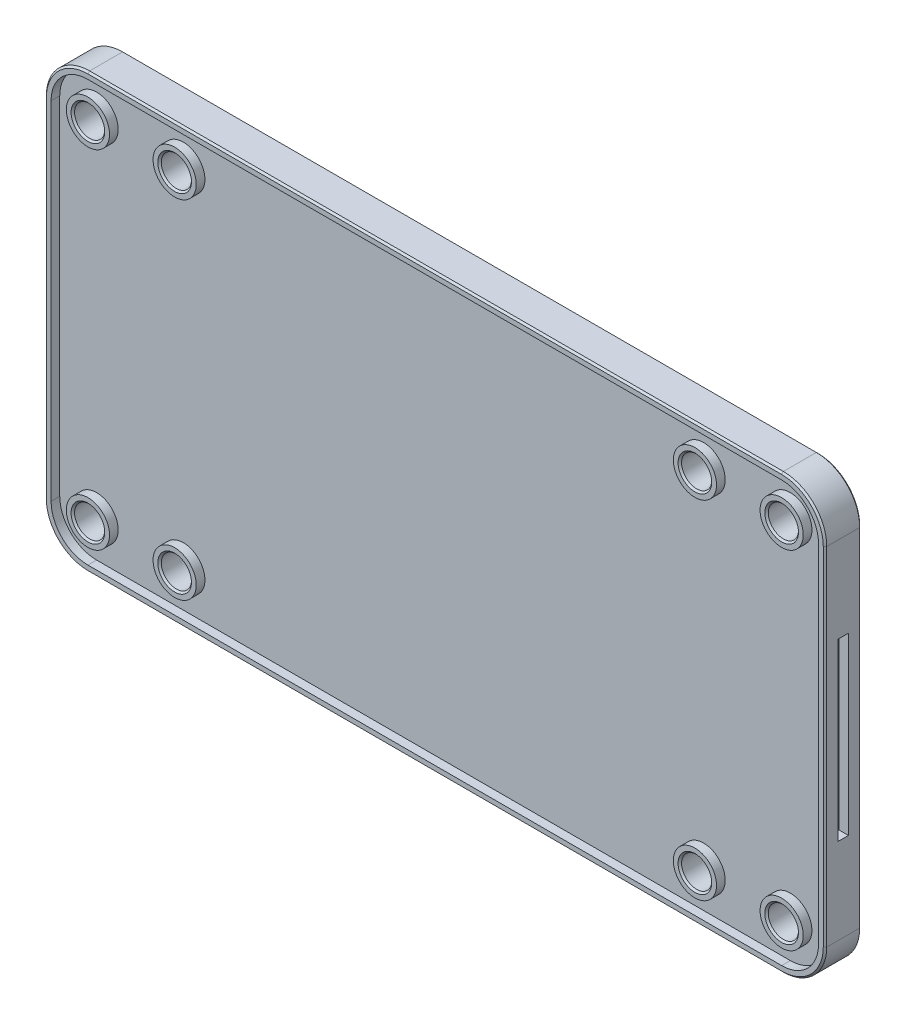
SolidWorks part; units mm, degrees
material "ABS"
ref_plane "Front Plane" through (0, 0, 0) normal (0, 0, 1) x (1, 0, 0)
ref_plane "Top Plane" through (0, 0, 0) normal (0, 1, 0) x (1, 0, 0)
ref_plane "Right Plane" through (0, 0, 0) normal (1, 0, 0) x (0, 0, -1)
sketch "Sketch1" plane through (0, 0, 0) normal (0, 0, 1) x (1, 0, 0)
  line L0 (-57.15, 0) -> (57.15, 0) construction
  line L1 (-50.8, -31.75) -> (50.8, -31.75)
  line L2 (-57.15, -25.4) -> (-57.15, 25.4)
  line L3 (-50.8, 31.75) -> (50.8, 31.75)
  line L4 (57.15, -25.4) -> (57.15, 25.4)
  line L5 (-57.15, -31.75) -> (57.15, 31.75) construction
  line L6 (-57.15, 31.75) -> (57.15, -31.75) construction
  line L7 (0, 31.75) -> (0, -31.75) construction
  arc A0 (50.8, 31.75) -> (57.15, 25.4) centre (50.8, 25.4) cw
  arc A1 (50.8, -31.75) -> (57.15, -25.4) centre (50.8, -25.4) ccw
  arc A2 (-50.8, -31.75) -> (-57.15, -25.4) centre (-50.8, -25.4) cw
  arc A3 (-57.15, 25.4) -> (-50.8, 31.75) centre (-50.8, 25.4) cw
  circle A4 centre (-50.8, -25.4) radius 2.2098
  circle A5 centre (-38.1, -25.4) radius 2.2098
  circle A6 centre (-50.8, 25.4) radius 2.2098
  circle A7 centre (-38.1, 25.4) radius 2.2098
  circle A8 centre (50.8, 25.4) radius 2.2098
  circle A9 centre (38.1, 25.4) radius 2.2098
  circle A10 centre (50.8, -25.4) radius 2.2098
  circle A11 centre (38.1, -25.4) radius 2.2098
  point P0 (0, 0)
  dimension "D3" = 6.35
  dimension "D4" = 4.4196
  dimension "D1" = 63.5
  dimension "D2" = 114.3
  dimension "D5" = 6.35
  dimension "D6" = 12.7
  dimension "D7" = 6.35
extrude "Boss-Extrude1" add sketch "Sketch1" against normal blind 3.175
sketch "Sketch2" plane through (0, 0, 0) normal (0, 0, 1) x (1, 0, 0)
  line L12 (50.8, 30.7975) -> (-50.8, 30.7975)
  line L13 (-56.1975, 25.4) -> (-56.1975, -25.4)
  line L14 (-50.8, -30.7975) -> (50.8, -30.7975)
  line L15 (56.1975, -25.4) -> (56.1975, 25.4)
  line L16 (50.8, 30.7975) -> (-50.8, 30.7975)
  line L17 (-56.1975, 25.4) -> (-56.1975, -25.4)
  line L18 (-50.8, -30.7975) -> (50.8, -30.7975)
  line L19 (56.1975, -25.4) -> (56.1975, 25.4)
  circle A0 centre (-50.8, -25.4) radius 2.2098 construction
  arc A8 (56.1975, 25.4) -> (50.8, 30.7975) centre (50.8, 25.4) ccw
  arc A9 (-50.8, 30.7975) -> (-56.1975, 25.4) centre (-50.8, 25.4) ccw
  arc A10 (-56.1975, -25.4) -> (-50.8, -30.7975) centre (-50.8, -25.4) ccw
  arc A11 (50.8, -30.7975) -> (56.1975, -25.4) centre (50.8, -25.4) ccw
  arc A12 (56.1975, 25.4) -> (50.8, 30.7975) centre (50.8, 25.4) ccw
  arc A13 (-50.8, 30.7975) -> (-56.1975, 25.4) centre (-50.8, 25.4) ccw
  arc A14 (-56.1975, -25.4) -> (-50.8, -30.7975) centre (-50.8, -25.4) ccw
  arc A15 (50.8, -30.7975) -> (56.1975, -25.4) centre (50.8, -25.4) ccw
  circle A36 centre (38.1, 25.4) radius 3.1623
  circle A37 centre (50.8, 25.4) radius 3.1623
  circle A38 centre (50.8, -25.4) radius 3.1623
  circle A39 centre (38.1, -25.4) radius 3.1623
  circle A40 centre (-38.1, -25.4) radius 3.1623
  circle A41 centre (-50.8, -25.4) radius 3.1623
  circle A42 centre (-38.1, 25.4) radius 3.1623
  circle A43 centre (-50.8, 25.4) radius 3.1623
  circle A44 centre (-38.1, -25.4) radius 2.2098 construction
  circle A47 centre (38.1, -25.4) radius 2.2098 construction
  circle A50 centre (50.8, -25.4) radius 2.2098 construction
  circle A51 centre (50.8, 25.4) radius 2.2098 construction
  circle A52 centre (38.1, 25.4) radius 2.2098 construction
  circle A53 centre (-38.1, 25.4) radius 2.2098 construction
  circle A54 centre (-50.8, 25.4) radius 2.2098 construction
  dimension "D2" = 0.9525
  dimension "D1" = 0.9525
extrude "Cut-Extrude3" cut sketch "Sketch2" against normal blind 1.27
sketch "Sketch3" plane through (0, 0, -3.175) normal (0, 0, -1) x (-1, 0, 0)
  line L4 (-57.15, 25.4) -> (-57.15, -25.4)
  line L5 (-50.8, -31.75) -> (50.8, -31.75)
  line L6 (57.15, -25.4) -> (57.15, 25.4)
  line L7 (50.8, 31.75) -> (-50.8, 31.75)
  line L8 (-57.15, 25.4) -> (-57.15, -25.4)
  line L9 (-50.8, -31.75) -> (50.8, -31.75)
  line L10 (57.15, -25.4) -> (57.15, 25.4)
  line L11 (50.8, 31.75) -> (-50.8, 31.75)
  circle A0 centre (-50.8, -25.4) radius 2.2098 construction
  circle A1 centre (-38.1, -25.4) radius 2.2098 construction
  circle A2 centre (38.1, -25.4) radius 2.2098 construction
  circle A3 centre (50.8, -25.4) radius 2.2098 construction
  arc A4 (-50.8, 31.75) -> (-57.15, 25.4) centre (-50.8, 25.4) ccw
  arc A5 (-57.15, -25.4) -> (-50.8, -31.75) centre (-50.8, -25.4) ccw
  arc A6 (50.8, -31.75) -> (57.15, -25.4) centre (50.8, -25.4) ccw
  arc A7 (57.15, 25.4) -> (50.8, 31.75) centre (50.8, 25.4) ccw
  arc A8 (-50.8, 31.75) -> (-57.15, 25.4) centre (-50.8, 25.4) ccw
  arc A9 (-57.15, -25.4) -> (-50.8, -31.75) centre (-50.8, -25.4) ccw
  arc A10 (50.8, -31.75) -> (57.15, -25.4) centre (50.8, -25.4) ccw
  arc A11 (57.15, 25.4) -> (50.8, 31.75) centre (50.8, 25.4) ccw
  circle A12 centre (50.8, 25.4) radius 2.2098 construction
  circle A13 centre (38.1, 25.4) radius 2.2098 construction
  circle A14 centre (-38.1, 25.4) radius 2.2098 construction
  circle A15 centre (-50.8, 25.4) radius 2.2098 construction
  circle A16 centre (-50.8, -25.4) radius 2.2098
  circle A17 centre (-38.1, -25.4) radius 2.2098
  circle A18 centre (38.1, -25.4) radius 2.2098
  circle A19 centre (50.8, -25.4) radius 2.2098
  circle A20 centre (50.8, 25.4) radius 2.2098
  circle A21 centre (38.1, 25.4) radius 2.2098
  circle A22 centre (-38.1, 25.4) radius 2.2098
  circle A23 centre (-50.8, 25.4) radius 2.2098
  dimension "D1" = 0
extrude "Boss-Extrude2" add sketch "Sketch3" along normal blind 2.159
sketch "Sketch4" plane through (57.15, 0, 0) normal (1, 0, 0) x (0, 0, -1)
  line L0 (5.334, -25.4) -> (0, -25.4) construction
  line L1 (1.905, 12.827) -> (3.429, 12.827)
  line L2 (1.905, 12.827) -> (1.905, -12.827)
  line L3 (1.905, -12.827) -> (3.429, -12.827)
  line L4 (3.429, 12.827) -> (3.429, -12.827)
  line L5 (5.334, 25.4) -> (5.334, -25.4) construction
  point P6 (2.667, -25.4)
  point P7 (2.667, -12.827)
  point P8 (1.905, 0)
  dimension "D1" = 1.524
  dimension "D2" = 25.654
extrude "Cut-Extrude4" cut sketch "Sketch4" against normal blind 1.397
mirror "Mirror1" about plane through (0, 0, 0) normal (1, 0, 0) of "Cut-Extrude4"
sketch "Sketch5" plane through (0, 0, -5.334) normal (0, 0, -1) x (-1, 0, 0)
  circle A0 centre (0, 0) radius 12.7
  dimension "D1" = 25.4
extrude "Cut-Extrude5" cut sketch "Sketch5" against normal blind 2.54
chamfer "Chamfer1" distance 0.254 angle 45 33 edges at (48.5902, 25.4, -5.334) (-40.3098, 25.4, -5.334) (-53.0098, -25.4, -5.334) (35.8902, -25.4, -5.334) (0, 31.75, -5.334) (-55.2901, 29.8901, -5.334) (-57.15, 0, -5.334) (-55.2901, -29.8901, -5.334) (0, -31.75, -5.334) (55.2901, -29.8901, -5.334) (57.15, 0, -5.334) (55.2901, 29.8901, -5.334) (48.5902, -25.4, -5.334) (-40.3098, -25.4, -5.334) (-53.0098, 25.4, -5.334) (35.8902, 25.4, -5.334) (-12.7, 0, -5.334) (-40.3098, 25.4, 0) (-53.0098, 25.4, 0) (-48.5902, -25.4, 0) (-35.8902, -25.4, 0) (48.5902, -25.4, 0) (35.8902, -25.4, 0) (40.3098, 25.4, 0) (53.0098, 25.4, 0) (-57.15, 0, 0) (-55.2901, -29.8901, 0) (-55.2901, 29.8901, 0) (0, -31.75, 0) (0, 31.75, 0) (55.2901, -29.8901, 0) (55.2901, 29.8901, 0) (57.15, 0, 0)
equation "\"tolerance\"= 0.005"
equation "\"D4@Sketch1\"=0.164 + \"tolerance\" * 2"
equation "\"D1@Boss-Extrude2\"= 0.080000in + \"tolerance\""
equation "\"D1@Sketch4\" = 0.05 + \"tolerance\" * 2"
equation "\"D2@Sketch4\" = 1 + \"tolerance\" * 2"
equation "\"D1@Cut-Extrude4\"= 0.05 + \"tolerance\""
